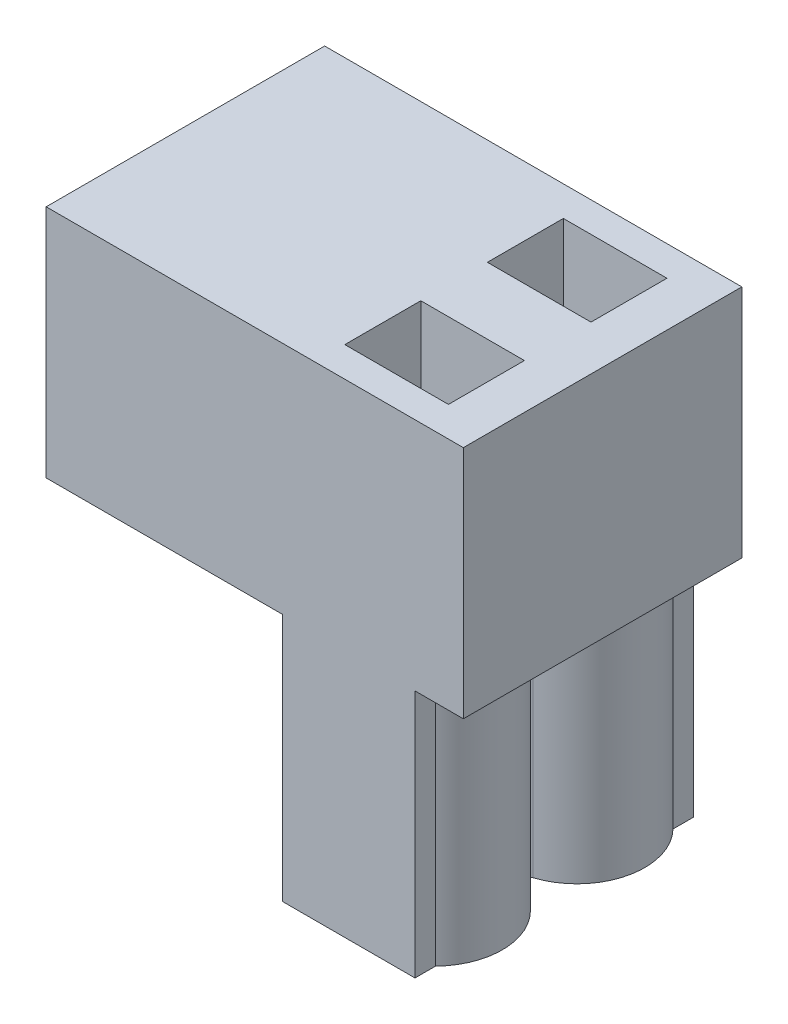
SolidWorks part; units mm, degrees
ref_plane "Front Plane" through (0, 0, 0) normal (0, 0, 1) x (1, 0, 0)
ref_plane "Top Plane" through (0, 0, 0) normal (0, 1, 0) x (1, 0, 0)
ref_plane "Right Plane" through (0, 0, 0) normal (1, 0, 0) x (0, 0, -1)
sketch "Sketch1" plane through (0, 0, 0) normal (0, 1, 0) x (1, 0, 0)
  line L1 (-7.55, -5.04) -> (7.55, -5.04)
  line L2 (-7.55, -5.04) -> (-7.55, 5.04)
  line L3 (-7.55, 5.04) -> (7.55, 5.04)
  line L4 (7.55, -5.04) -> (7.55, 5.04)
  line L5 (-7.55, -5.04) -> (7.55, 5.04) construction
  line L6 (-7.55, 5.04) -> (7.55, -5.04) construction
  point P0 (0, 0)
  dimension "D1" = 15.1
  dimension "D2" = 10.08
extrude "Boss-Extrude1" add sketch "Sketch1" along normal blind 8.5
sketch "Sketch2" plane through (0, 0, 0) normal (0, -1, 0) x (1, 0, 0)
  line L0 (4.04, 2.58) -> (7.55, 2.58) construction
  line L1 (7.55, 5.04) -> (7.55, -5.04) construction
  line L2 (5.8, 4.2987) -> (5.8, 5.04)
  line L3 (5.8, 5.04) -> (1, 5.04)
  line L4 (1, 5.04) -> (1, 4.04)
  line L5 (1, 4.04) -> (1.75, 4.04)
  line L6 (1.75, 4.04) -> (1.75, 1.12)
  line L7 (-7.55, 5.04) -> (7.55, 5.04) construction
  line L8 (7.55, 0) -> (-7.55, 0) construction
  line L9 (-7.55, -5.04) -> (-7.55, 5.04) construction
  line L10 (1, 1.12) -> (1.75, 1.12)
  line L11 (1, -1.12) -> (1, 1.12)
  line L12 (4.04, 0) -> (4.04, 5.04) construction
  line L13 (1, -1.12) -> (1.75, -1.12)
  line L14 (1.75, -4.04) -> (1.75, -1.12)
  line L15 (1, -4.04) -> (1.75, -4.04)
  line L16 (1, -5.04) -> (1, -4.04)
  line L17 (5.8, -5.04) -> (1, -5.04)
  line L18 (5.8, -4.2987) -> (5.8, -5.04)
  arc A0 (4.7928, 0.238) -> (5.8, 4.2987) centre (4.04, 2.58) ccw
  circle A1 centre (4.04, 2.58) radius 0.55
  arc A2 (4.7928, -0.238) -> (5.8, -4.2987) centre (4.04, -2.58) cw
  arc A3 (4.7928, 0.238) -> (4.7928, -0.238) centre (4.8693, 0) ccw
  circle A4 centre (4.04, -2.58) radius 0.55
  point P12 (6.5, 2.58)
  point P25 (1, 0)
  dimension "D4" = 2.58
  dimension "D5" = 1.1
  dimension "D8" = 0.25
  dimension "D1" = 5.5
  dimension "D2" = 1.05
  dimension "D3" = 1.75
  dimension "D6" = 0.75
  dimension "D7" = 1
extrude "Boss-Extrude2" add sketch "Sketch2" along normal blind 9
sketch "Sketch3" plane through (-7.55, 0, 0) normal (-1, 0, 0) x (0, 0, 1)
  line L0 (0, 8.5) -> (0, 0) construction
  line L1 (-5.04, 8.5) -> (5.04, 8.5) construction
  line L2 (-5.04, 0) -> (5.04, 0) construction
  line L3 (-4.4308, 3.525) -> (-0.7292, 3.525)
  line L4 (-4.455, 3.225) -> (-0.705, 3.225) construction
  line L5 (-4.4308, 2.925) -> (-0.7292, 2.925)
  line L6 (4.4308, 2.925) -> (0.7292, 2.925)
  line L7 (4.4308, 3.525) -> (0.7292, 3.525)
  circle A0 centre (-2.58, 3.225) radius 1.875
  circle A1 centre (2.58, 3.225) radius 1.875
  point P8 (-2.58, 5.1)
  dimension "D1" = 3.75
  dimension "D2" = 2.58
  dimension "D3" = 3.4
  dimension "D4" = 0.6
extrude "Cut-Extrude1" cut sketch "Sketch3" against normal blind 2 contours A0 | A1
extrude "Cut-Extrude2" cut sketch "Sketch3<3>" against normal blind 2.75 contours L3 A0 L5 | A1 L6 L7 region at (-7.55, 3.225, -2.58) region at (-7.55, 3.225, 2.58)
sketch "Sketch3<3>" plane through (-7.55, 0, 0) normal (-1, 0, 0) x (0, 0, 1) same geometry as "Sketch3"
sketch "Sketch4" plane through (0, 8.5, 0) normal (0, 1, 0) x (1, 0, 0)
  line L0 (7.55, 0) -> (-7.55, 0) construction
  line L1 (7.55, -5.04) -> (7.55, 5.04) construction
  line L2 (-7.55, 5.04) -> (-7.55, -5.04) construction
  line L3 (2.175, -1.205) -> (5.925, -1.205)
  line L4 (2.175, 3.955) -> (5.925, 3.955)
  line L5 (2.175, 3.955) -> (2.175, 1.205)
  line L6 (2.175, 1.205) -> (5.925, 1.205)
  line L7 (5.925, 3.955) -> (5.925, 1.205)
  line L8 (2.175, 3.955) -> (5.925, 1.205) construction
  line L9 (2.175, 1.205) -> (5.925, 3.955) construction
  line L10 (2.175, -3.955) -> (2.175, -1.205)
  line L11 (2.175, -3.955) -> (5.925, -3.955)
  line L12 (5.925, -3.955) -> (5.925, -1.205)
  point P6 (4.05, 2.58)
  dimension "D1" = 2.75
  dimension "D2" = 3.75
  dimension "D3" = 2.58
  dimension "D4" = 3.5
extrude "Cut-Extrude3" cut sketch "Sketch4" against normal blind 2.9
